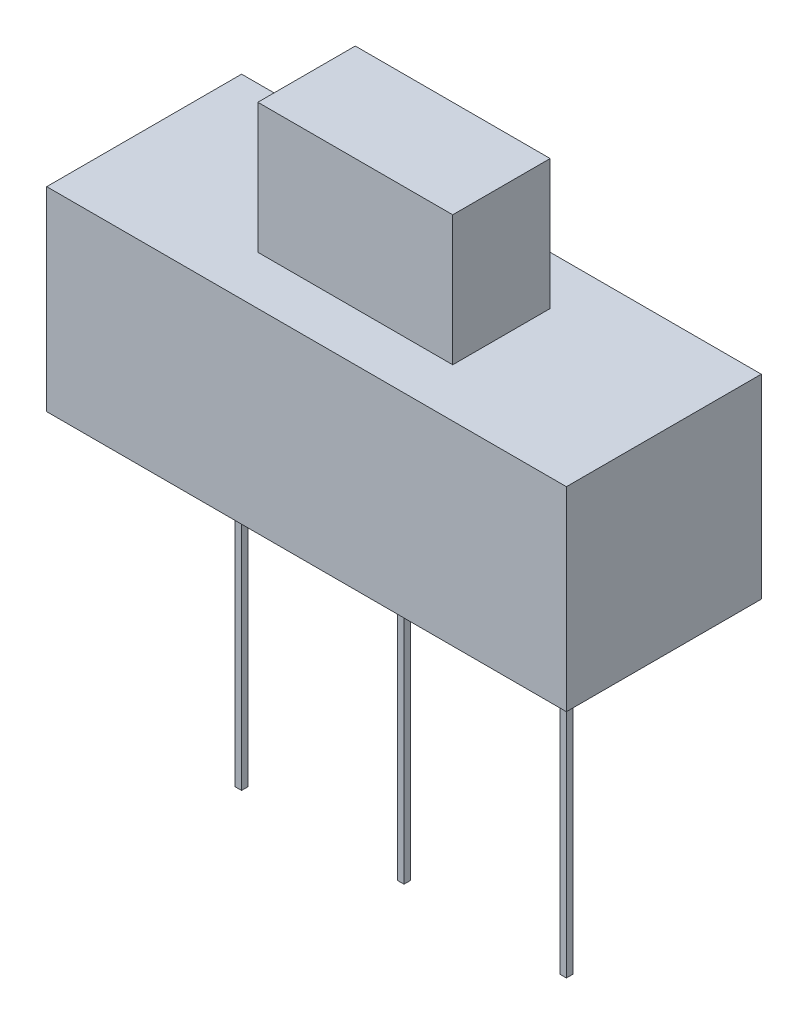
SolidWorks part; units mm, degrees
ref_plane "Front Plane" through (0, 0, 0) normal (0, 0, 1) x (1, 0, 0)
ref_plane "Top Plane" through (0, 0, 0) normal (0, 1, 0) x (1, 0, 0)
ref_plane "Right Plane" through (0, 0, 0) normal (1, 0, 0) x (0, 0, -1)
sketch "Sketch1" plane through (0, 0, 0) normal (0, 1, 0) x (1, 0, 0)
  line L1 (-4, -1.5) -> (4, -1.5)
  line L2 (-4, -1.5) -> (-4, 1.5)
  line L3 (-4, 1.5) -> (4, 1.5)
  line L4 (4, -1.5) -> (4, 1.5)
  line L5 (-4, -1.5) -> (4, 1.5) construction
  line L6 (-4, 1.5) -> (4, -1.5) construction
  point P0 (0, 0)
  dimension "D1" = 8
  dimension "D2" = 3
extrude "Boss-Extrude1" add sketch "Sketch1" along normal blind 3
sketch "Sketch2" plane through (0, 3, 0) normal (0, 1, 0) x (1, 0, 0)
  line L1 (-1.5, -0.75) -> (1.5, -0.75)
  line L2 (-1.5, -0.75) -> (-1.5, 0.75)
  line L3 (-1.5, 0.75) -> (1.5, 0.75)
  line L4 (1.5, -0.75) -> (1.5, 0.75)
  line L5 (-1.5, -0.75) -> (1.5, 0.75) construction
  line L6 (-1.5, 0.75) -> (1.5, -0.75) construction
  point P0 (0, 0)
  dimension "D1" = 3
  dimension "D2" = 1.5
extrude "Boss-Extrude2" add sketch "Sketch2" along normal blind 2
sketch "Sketch3" plane through (0, 0, 0) normal (0, -1, 0) x (1, 0, 0)
  line L0 (2.45, -0.05) -> (2.45, 0.05)
  line L1 (-0.05, -0.05) -> (0.05, -0.05)
  line L2 (-0.05, -0.05) -> (-0.05, 0.05)
  line L3 (-0.05, 0.05) -> (0.05, 0.05)
  line L4 (0.05, -0.05) -> (0.05, 0.05)
  line L5 (-0.05, -0.05) -> (0.05, 0.05) construction
  line L6 (-0.05, 0.05) -> (0.05, -0.05) construction
  line L7 (2.45, -0.05) -> (2.55, -0.05)
  line L8 (2.55, -0.05) -> (2.55, 0.05)
  line L9 (2.45, 0.05) -> (2.55, 0.05)
  line L10 (-0.05, -0.05) -> (-0.05, 0.05)
  line L11 (-0.05, -0.05) -> (0.05, -0.05)
  line L12 (0.05, -0.05) -> (0.05, 0.05)
  line L13 (-0.05, 0.05) -> (0.05, 0.05)
  line L14 (-2.55, -0.05) -> (-2.55, 0.05)
  line L15 (-2.55, -0.05) -> (-2.45, -0.05)
  line L16 (-2.45, -0.05) -> (-2.45, 0.05)
  line L17 (-2.55, 0.05) -> (-2.45, 0.05)
  point P0 (0, 0)
  dimension "D1" = 0.1
  dimension "D2" = 0.1
  dimension "D3" = 2
  dimension "D4" = 2
extrude "Boss-Extrude3" add sketch "Sketch3" along normal blind 5 contours L9 L0 L7 L8 | L1 L4 L3 L2 | L17 L14 L15 L16 region at (2.5, 0, 0) region at (0, 0, 0) region at (-2.5, 0, 0)
